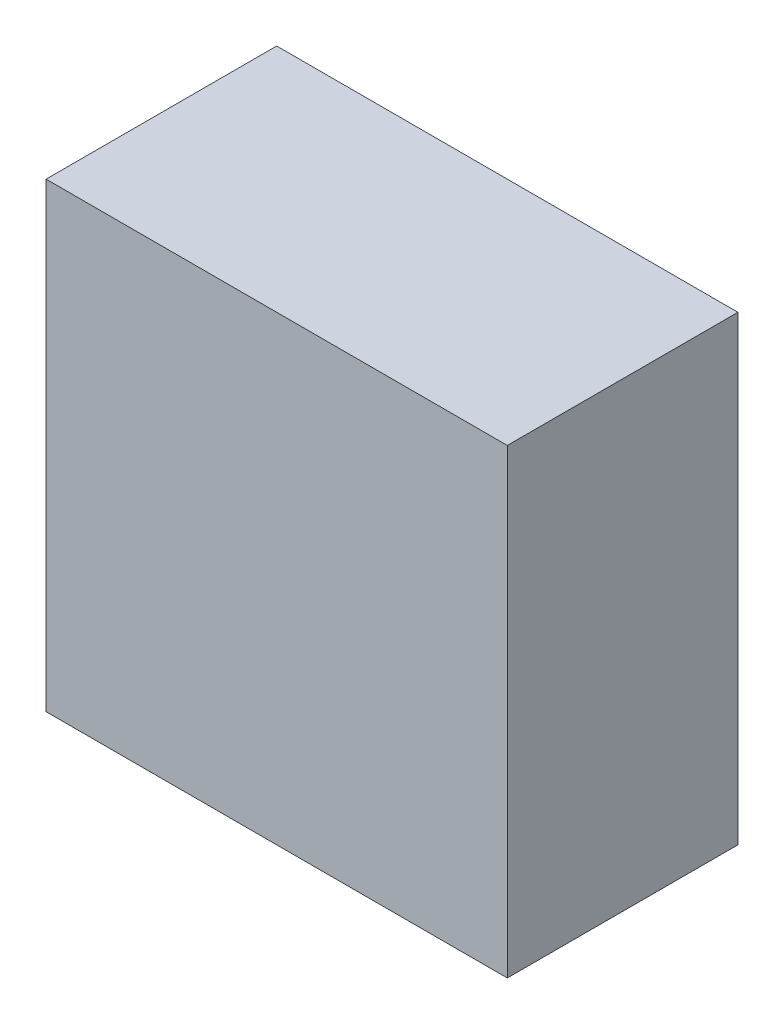
SolidWorks part; units mm, degrees
ref_plane "Front Plane" through (0, 0, 0) normal (0, 0, 1) x (1, 0, 0)
ref_plane "Top Plane" through (0, 0, 0) normal (0, 1, 0) x (1, 0, 0)
ref_plane "Right Plane" through (0, 0, 0) normal (1, 0, 0) x (0, 0, -1)
sketch "Sketch1" plane through (0, 0, 0) normal (0, 0, 1) x (1, 0, 0)
  line L1 (0, 0) -> (40, 0)
  line L2 (0, 0) -> (0, 40)
  line L3 (0, 40) -> (40, 40)
  line L4 (40, 0) -> (40, 40)
extrude "Boss-Extrude1" add sketch "Sketch1" along normal blind 10 and the other way blind 10
sketch "Sketch2" plane through (0, 0, 0) normal (0, 0, 1) x (1, 0, 0)
  line L1 (0, 0) -> (10, 0)
  line L2 (0, 0) -> (0, 10)
  line L3 (0, 10) -> (10, 10)
  line L4 (10, 0) -> (10, 10)
extrude "Cut-Extrude1" cut sketch "Sketch2" against normal blind 5
